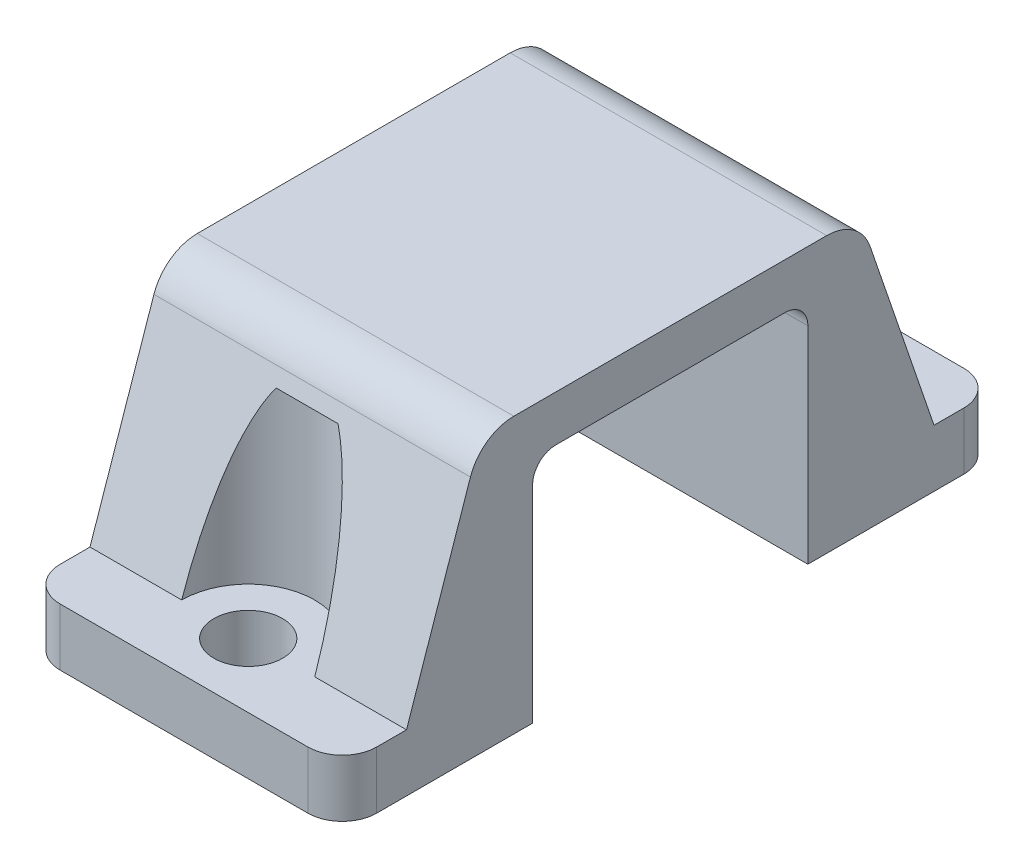
SolidWorks part; units mm, degrees
ref_plane "Alzado" through (0, 0, 0) normal (0, 0, 1) x (1, 0, 0)
ref_plane "Planta" through (0, 0, 0) normal (0, 1, 0) x (1, 0, 0)
ref_plane "Vista lateral" through (0, 0, 0) normal (1, 0, 0) x (0, 0, -1)
sketch "Croquis1" plane through (0, 0, 0) normal (1, 0, 0) x (0, 0, -1)
  line L0 (-6, 0) -> (6, 0)
  line L1 (6, 0) -> (6, -10)
  line L2 (14.3, -10) -> (6, -10)
  line L3 (14.3, -10) -> (14.3, -7.5)
  line L4 (14.3, -7.5) -> (11.5, -7.5)
  line L6 (8.25, 2) -> (-8.25, 2)
  line L7 (-6, 0) -> (-6, -10)
  line L8 (-6, -10) -> (-14.3, -10)
  line L9 (-14.3, -10) -> (-14.3, -7.5)
  line L10 (-14.3, -7.5) -> (-11.5, -7.5)
  line L12 (8.25, 2) -> (11.5, -7.5)
  line L13 (-8.25, 2) -> (-11.5, -7.5)
  point P4 (0, 0)
  point P12 (0, 2)
  dimension "D1" = 12
  dimension "D2" = 16.5
  dimension "D3" = 2.5
  dimension "D4" = 10
  dimension "D5" = 8.3
  dimension "D6" = 12
  dimension "D7" = 8.3
  dimension "D8" = 2.5
  dimension "D9" = 5.5
  dimension "D10" = 5.5
  dimension "D11" = 12
extrude "Saliente-Extruir1" add sketch "Croquis1" along normal blind 13.8
sketch "Croquis3" plane through (0, 0, 0) normal (0, 1, 0) x (1, 0, 0)
  line L0 (13.8, -11.5) -> (0, -11.5) construction
  line L5 (13.8, 11.5) -> (0, 11.5) construction
  circle A0 centre (6.9, -11.5) radius 1.5
  circle A1 centre (6.9, -11.5) radius 2.9
  circle A2 centre (6.9, 11.5) radius 2.9
  circle A3 centre (6.9, 11.5) radius 1.5
  dimension "D1" = 3
  dimension "D2" = 5.8
  dimension "D3" = 2
extrude "Cortar-Extruir1" cut sketch "Croquis3" against normal up to surface (10 mm away) contours A0 | A3 region at (6.9, 0, 11.5) region at (6.9, 0, -11.5) up to face at (6.9, -10, 10.15)
extrude "Cortar-Extruir2" cut sketch "Croquis3<3>" against normal up to surface (7.5 mm away) contours A1 A0 | A2 A3 region at (4.082, 0, 11.5) region at (4.082, 0, -11.5) up to face at (6.9, -7.5, 12.6833)
sketch "Croquis3<3>" plane through (0, 0, 0) normal (0, 1, 0) x (1, 0, 0) same geometry as "Croquis3"
fillet "Redondeo1" radius 1 2 edges at (6.9, 0, 6) (6.9, 0, -6)
fillet "Redondeo2" radius 2 2 edges at (6.9, 2, -8.25) (6.9, 2, 8.25)
fillet "Redondeo3" radius 1.5 4 edges at (0, -8.75, 14.3) (13.8, -8.75, 14.3) (13.8, -8.75, -14.3) (0, -8.75, -14.3)
